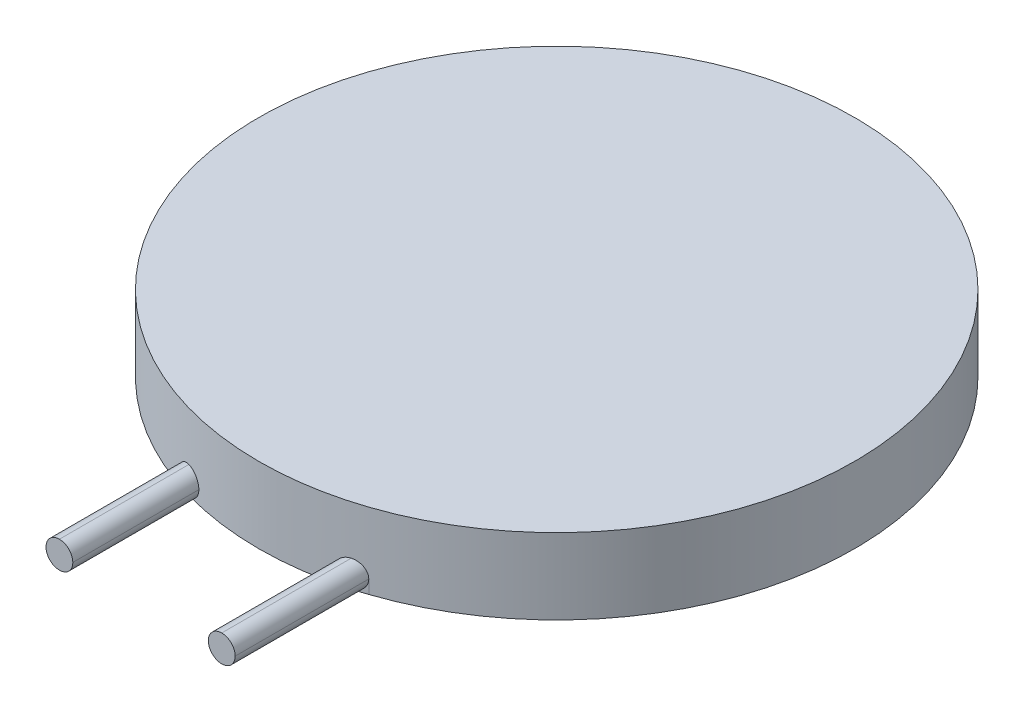
SolidWorks part; units mm, degrees
ref_plane "Front Plane" through (0, 0, 0) normal (0, 0, 1) x (1, 0, 0)
ref_plane "Top Plane" through (0, 0, 0) normal (0, 1, 0) x (1, 0, 0)
ref_plane "Right Plane" through (0, 0, 0) normal (1, 0, 0) x (0, 0, -1)
sketch "Sketch1" plane through (0, 0, 0) normal (0, 1, 0) x (1, 0, 0)
  circle A0 centre (0, 0) radius 20.0025
  dimension "D1" = 40.005
extrude "Boss-Extrude1" add sketch "Sketch1" along normal blind 5.08
sketch "Sketch2" plane through (0, 0, 0) normal (0, -1, 0) x (1, 0, 0)
  line L0 (-4.55, 12.7) -> (4.55, 12.7) construction
  line L1 (-4.55, 12.7) -> (-6.35, 12.7)
  line L2 (-4.55, 12.7) -> (-4.55, 27.94)
  line L3 (-4.55, 27.94) -> (-6.35, 27.94)
  line L4 (-6.35, 12.7) -> (-6.35, 27.94)
  line L5 (4.55, 12.7) -> (6.35, 12.7)
  line L6 (4.55, 12.7) -> (4.55, 27.94)
  line L7 (4.55, 27.94) -> (6.35, 27.94)
  line L8 (6.35, 12.7) -> (6.35, 27.94)
  line L9 (0, 12.7) -> (0, 0) construction
  dimension "D1" = 1.8
  dimension "D2" = 1.8
  dimension "D3" = 12.7
  dimension "D4" = 12.7
  dimension "D5" = 15.24
  dimension "D6" = 15.24
extrude "Boss-Extrude2" add sketch "Sketch2" against normal blind 1.8
fillet "Fillet1" radius 0.9 8 edges at (6.35, 1.8, 23.4539) (6.35, 0, 23.4539) (4.55, 1.8, 23.7091) (4.55, 0, 23.7091) (-6.35, 1.8, 23.4539) (-4.55, 1.8, 23.7091) (-6.35, 0, 23.4539) (-4.55, 0, 23.7091)
